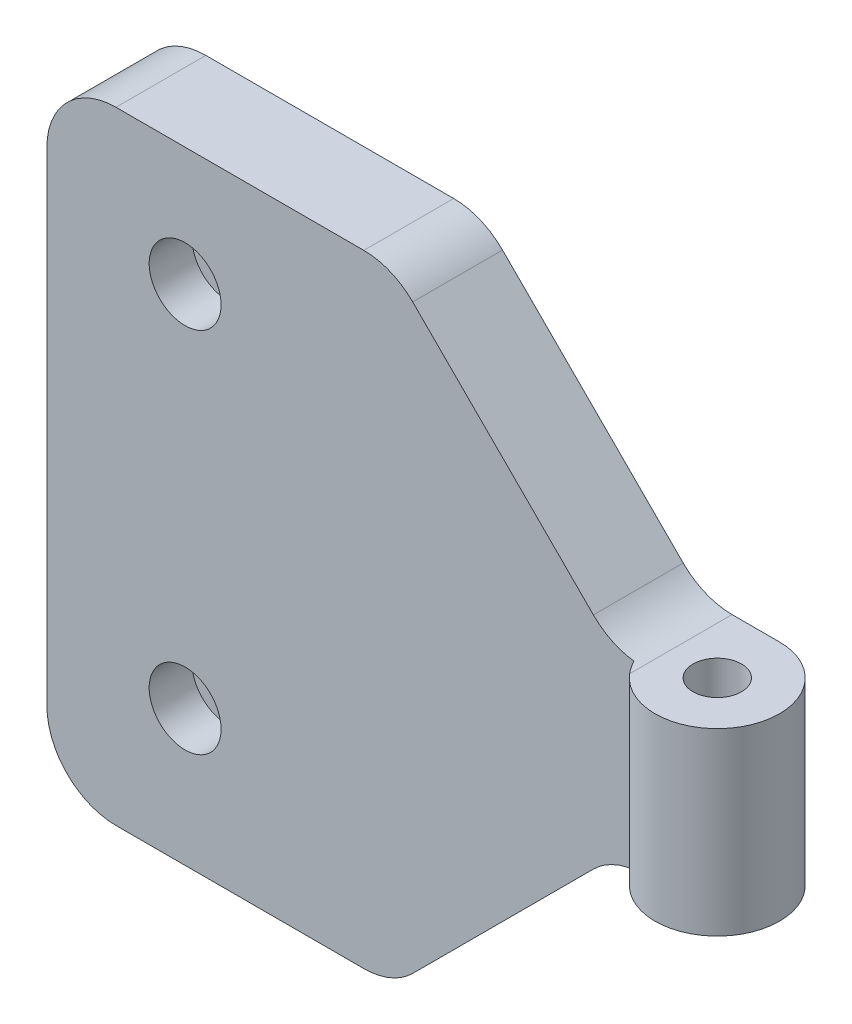
SolidWorks part; units mm, degrees
note: The reader was unsure of these and kept them because the rebuilt part matched: shared geometry of "Sketch1<3>", "Sketch5<4>".
ref_plane "Front Plane" through (0, 0, 0) normal (0, 0, 1) x (1, 0, 0)
ref_plane "Top Plane" through (0, 0, 0) normal (0, 1, 0) x (1, 0, 0)
ref_plane "Right Plane" through (0, 0, 0) normal (1, 0, 0) x (0, 0, -1)
sketch "Sketch1" plane through (0, 0, 0) normal (0, 1, 0) x (1, 0, 0)
  line L0 (-46.5, -2.5) -> (-46.5, 4.5)
  line L1 (-6.5, -2.5) -> (-30.1023, -2.5) construction
  line L2 (-6.5, -2.5) -> (-6.5, -6.5) construction
  line L3 (-6.5, -6.5) -> (-30.1023, -6.5) construction
  line L4 (-30.1023, -2.5) -> (-30.1023, -6.5) construction
  line L5 (-6.5, -6.5) -> (-2.5, -6.5) construction
  line L6 (-6.5, -6.5) -> (-6.5, -30.1023) construction
  line L7 (-6.5, -30.1023) -> (-2.5, -30.1023) construction
  line L8 (-2.5, -6.5) -> (-2.5, -30.1023) construction
  line L9 (-46.5, 4.5) -> (0, 4.5)
  line L10 (-2.5, -46.5) -> (4.5, -46.5)
  line L11 (4.5, -46.5) -> (4.5, 0)
  line L12 (0, 0) -> (-6.5, -6.5) construction
  line L13 (-46.5, -2) -> (-4.0311, -2)
  line L14 (-2, -46.5) -> (-2, -4.0311)
  line L16 (0, -3.3) -> (2.8579, -1.65)
  line L17 (2.8579, -1.65) -> (2.8579, 1.65)
  line L18 (2.8579, 1.65) -> (0, 3.3)
  line L19 (0, 3.3) -> (-2.8579, 1.65)
  line L20 (-2.8579, 1.65) -> (-2.8579, -1.65)
  line L21 (-2.8579, -1.65) -> (0, -3.3)
  circle A0 centre (0, 0) radius 4.5
  circle A1 centre (0, 0) radius 1.75
  circle A2 centre (0, 0) radius 2.8579 construction
  point P14 (0, 4.5)
  point P18 (4.5, 0)
  dimension "D2" = 9
  dimension "D7" = 3.5
  dimension "D1" = 4
  dimension "D3" = 7
  dimension "D4" = 40
  dimension "D5" = 0.5
  dimension "D6" = 0.5
  dimension "D8" = 3.3
extrude "Boss-Extrude1" add sketch "Sketch1" along normal blind 45 contours A0 L9 L0 L13
extrude "Boss-Extrude2" add sketch "Sketch1<3>" along normal blind 13 from offset 16 contours A0 L21 L20 L19 L18 L17 L16 | L20 L21 L16 L17 L18 L19 A1
sketch "Sketch1<3>" plane through (0, 0, 0) normal (0, 1, 0) x (1, 0, 0) same geometry as "Sketch1"
sketch "Sketch5" plane through (0, 0, 0) normal (0, 1, 0) x (1, 0, 0)
  line L0 (0, 0) -> (4.5, 0) construction
  line L1 (4.5, -4.5) -> (-4.5, -4.5) construction
  line L2 (4.5, -4.5) -> (4.5, 4.5) construction
  line L3 (4.5, 4.5) -> (-4.5, 4.5) construction
  line L4 (-4.5, -4.5) -> (-4.5, 4.5) construction
  line L5 (4.5, -4.5) -> (-4.5, 4.5) construction
  line L6 (4.5, 4.5) -> (-4.5, -4.5) construction
  line L7 (0, 0) -> (0, -4.5)
  circle A3 centre (0, 0) radius 5.5
  point P0 (0, 0)
  point P10 (4.5, 0)
  dimension "D1" = 11
extrude "Cut-Extrude1" cut sketch "Sketch5" against normal blind 25 from surface at 16 contours L1 L4 L3 L2 | A3
sketch "Sketch6" plane through (0, 0, 2) normal (0, 0, 1) x (1, 0, 0)
  line L0 (-36.5, 45) -> (-36.5, 0) construction
  line L1 (-46.5, 45) -> (-4.0311, 45) construction
  line L2 (-46.5, 0) -> (-5.1235, 0) construction
  line L3 (-46.5, 45) -> (-46.5, 0) construction
  circle A0 centre (-36.5, 36.4173) radius 2.6
  circle A1 centre (-36.5, 9.8329) radius 2.6
  dimension "D2" = 5.2
  dimension "D1" = 10
extrude "Cut-Extrude2" cut sketch "Sketch6" against normal blind 15
extrude "Cut-Extrude4" cut sketch "Sketch5<4>" along normal blind 20.4 from surface at 29 contours A3 starting at face at (0, 29, 0)
sketch "Sketch5<4>" plane through (0, 0, 0) normal (0, 1, 0) x (1, 0, 0) same geometry as "Sketch5"
fillet "Fillet1" radius 0.5 1 edges at (-3.1623, 8, -4.5)
fillet "Fillet2" radius 5 2 edges at (-46.5, 0, -1.25) (-46.5, 45, -1.25)
sketch "Sketch7" plane through (0, 0, -4.5) normal (0, 0, -1) x (-1, 0, 0)
  circle A0 centre (36.5, 36.4173) radius 5.5
  circle A1 centre (36.5, 9.8329) radius 5.5
  dimension "D1" = 11
extrude "Cut-Extrude3" cut sketch "Sketch7" against normal blind 3
sketch "Sketch8" plane through (0, 0, -1.5) normal (0, 0, -1) x (-1, 0, 0)
  circle A0 centre (36.5, 36.4173) radius 3.0011
  circle A1 centre (36.5, 9.8329) radius 3.7344
extrude "Boss-Extrude5" add sketch "Sketch8" against normal blind 0.4
sketch "Sketch9" plane through (0, 0, -4.5) normal (0, 0, -1) x (-1, 0, 0)
  line L0 (21.5, 45) -> (21.5, 29)
  line L1 (41.5, 45) -> (3.1623, 45) construction
  line L2 (21.5, 29) -> (-0.0504, 29)
  line L3 (-0.0504, 29) -> (-0.0504, 45)
  line L4 (-0.0504, 45) -> (21.5, 45)
  line L5 (4.4721, 16) -> (21.5, 16)
  line L6 (21.5, 16) -> (21.5, 0)
  line L7 (41.5, 0) -> (4.4721, 0) construction
  line L8 (21.5, 0) -> (2.2361, 0)
  line L9 (2.2361, 0) -> (2.2361, 16)
  line L10 (4.4721, 16) -> (0, 16) construction
  line L11 (2.2361, 16) -> (4.4721, 16)
  line L12 (5.5, 29) -> (21.5, 45)
  line L13 (46.5, 40) -> (46.5, 5) construction
  line L14 (3.1623, 29) -> (0, 29) construction
  line L15 (21.5, 0) -> (5.5, 16)
  line M8 (4.4721, 0) -> (41.5, 0)
  line M12 (41.5, 45) -> (3.1623, 45)
  line M13 (3.1623, 45) -> (3.1623, 29)
  line M14 (3.1623, 29) -> (0, 29)
  line M16 (0, 16) -> (4.4721, 16)
  line M17 (4.4721, 16) -> (4.4721, 0)
  dimension "D1" = 25
  dimension "D2" = 25
  dimension "D3" = 45
  dimension "D4" = 45
extrude "Cut-Extrude5" cut sketch "Sketch9" against normal blind 10 contours L15 L5 M8 M17 | L9 L8 M17 M16 | L4 L3 L2 M14 M13 | L2 L12 M12 M13
fillet "Fillet4" radius 5 4 edges at (-5.5, 29, -1.25) (-5.5, 16, -1.25) (-21.5, 0, -1.25) (-21.5, 45, -1.25)
